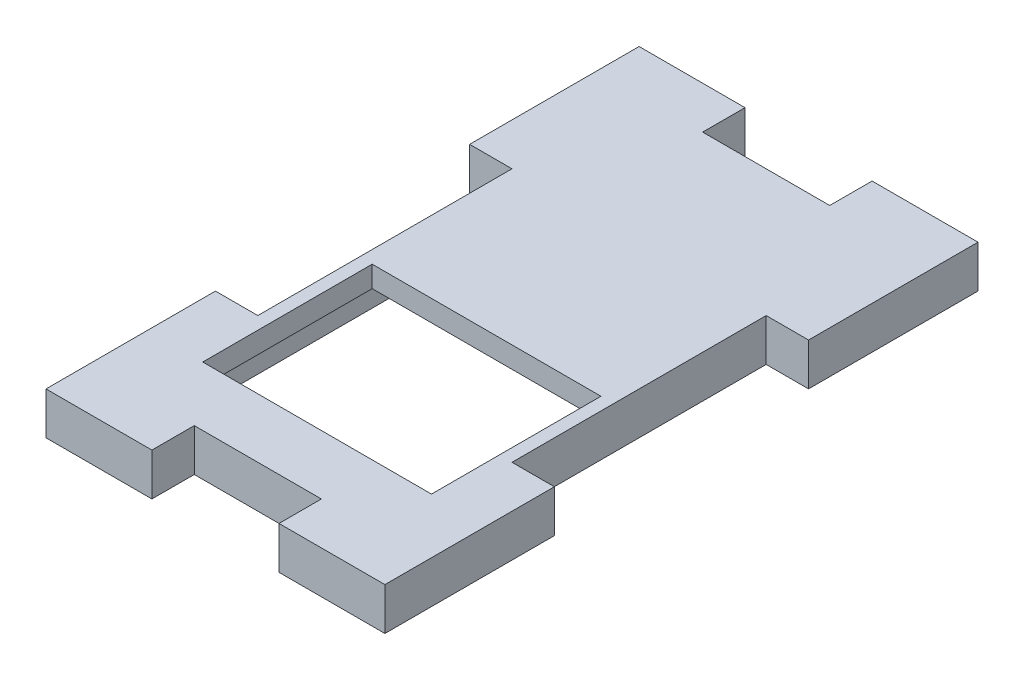
SolidWorks part; units mm, degrees
material "Acrylic (Medium-high impact)"
ref_plane "Front Plane" through (0, 0, 0) normal (0, 0, 1) x (1, 0, 0)
ref_plane "Top Plane" through (0, 0, 0) normal (0, 1, 0) x (1, 0, 0)
ref_plane "Right Plane" through (0, 0, 0) normal (1, 0, 0) x (0, 0, -1)
sketch "Sketch1" plane through (0, 0, 0) normal (0, 1, 0) x (1, 0, 0)
  line L1 (0, 0) -> (40, 0)
  line L2 (0, 0) -> (0, 70)
  line L3 (0, 70) -> (40, 70)
  line L4 (40, 0) -> (40, 70)
  line L5 (6.5, 12) -> (33.5, 12)
  line L6 (6.5, 12) -> (6.5, 32)
  line L7 (6.5, 32) -> (33.5, 32)
  line L8 (33.5, 12) -> (33.5, 32)
  point P9 (20, 70)
  point P10 (20, 32)
  dimension "D1" = 70
  dimension "D2" = 40
  dimension "D3" = 20
  dimension "D4" = 27
  dimension "D5" = 38
extrude "Boss-Extrude1" add sketch "Sketch1" along normal blind 5
sketch "Sketch2" plane through (0, 0, 0) normal (0, -1, 0) x (1, 0, 0)
  line L0 (0, -70) -> (0, 0) construction
  line L1 (6, -36) -> (34, -36)
  line L2 (6, -36) -> (6, -8)
  line L3 (6, -8) -> (34, -8)
  line L4 (34, -36) -> (34, -8)
  line L5 (6, -36) -> (34, -8) construction
  line L6 (6, -8) -> (34, -36) construction
  line L13 (6.5, -32) -> (6.5, -12) construction
  line L14 (6.5, -22) -> (33.5, -22) construction
  line L15 (33.5, -12) -> (33.5, -32) construction
  point P0 (20, -22)
  point P7 (0, 0)
  point P8 (0, 0)
  point P9 (20, -22)
  dimension "D1" = 6
  dimension "D2" = 28
extrude "Cut-Extrude1" cut sketch "Sketch2" against normal blind 2.5
sketch "Sketch3" plane through (0, 5, 0) normal (0, 1, 0) x (1, 0, 0)
  line L0 (6.5, 32) -> (33.5, 12) construction
  line L1 (8.25, 10.125) -> (31.75, 10.125) construction
  line L2 (8.25, 10.125) -> (8.25, 33.875) construction
  line L3 (8.25, 33.875) -> (31.75, 33.875) construction
  line L4 (31.75, 10.125) -> (31.75, 33.875) construction
  line L5 (8.25, 10.125) -> (31.75, 33.875) construction
  line L6 (8.25, 33.875) -> (31.75, 10.125) construction
  point P0 (20, 22)
  point P5 (20, 22)
  dimension "D1" = 23.75
  dimension "D2" = 23.5
sketch "Sketch4" plane through (0, 0, 0) normal (0, -1, 0) x (1, 0, 0)
  line L1 (30.75, -61) -> (9.25, -61)
  line L2 (30.75, -61) -> (30.75, -41.5)
  line L3 (30.75, -41.5) -> (9.25, -41.5)
  line L4 (9.25, -61) -> (9.25, -41.5)
  line L5 (30.75, -61) -> (9.25, -41.5) construction
  line L6 (30.75, -41.5) -> (9.25, -61) construction
  line L7 (40, -70) -> (0, -70) construction
  point P0 (20, -51.25)
  point P5 (29.6889, -58.5726)
  point P6 (0, 0)
  dimension "D1" = 19.5
  dimension "D2" = 21.5
  dimension "D4" = 9
extrude "Cut-Extrude2" cut sketch "Sketch4" against normal blind 2.5
sketch "Sketch5" plane through (0, 5, 0) normal (0, 1, 0) x (1, 0, 0)
  line L0 (0, 70) -> (0, 0) construction
  line L1 (0, 20) -> (5, 20)
  line L2 (0, 20) -> (0, 50)
  line L3 (0, 50) -> (5, 50)
  line L4 (5, 20) -> (5, 50)
  line L5 (40, 70) -> (0, 70) construction
  line L6 (27.5, 70) -> (12.5, 70)
  line L7 (27.5, 70) -> (27.5, 65)
  line L8 (27.5, 65) -> (12.5, 65)
  line L9 (12.5, 70) -> (12.5, 65)
  line L10 (40, 0) -> (40, 70) construction
  line L11 (40, 50) -> (35, 50)
  line L12 (40, 50) -> (40, 20)
  line L13 (40, 20) -> (35, 20)
  line L14 (35, 50) -> (35, 20)
  line L15 (0, 0) -> (40, 0) construction
  line L16 (12.5, 0) -> (27.5, 0)
  line L17 (12.5, 0) -> (12.5, 5)
  line L18 (12.5, 5) -> (27.5, 5)
  line L19 (27.5, 0) -> (27.5, 5)
  point P24 (35, 40.9428)
  point P25 (0, 35)
  point P26 (20, 0)
  dimension "D1" = 5
  dimension "D2" = 30
  dimension "D3" = 15
extrude "Cut-Extrude3" cut sketch "Sketch5" against normal through all both and the other way through all
